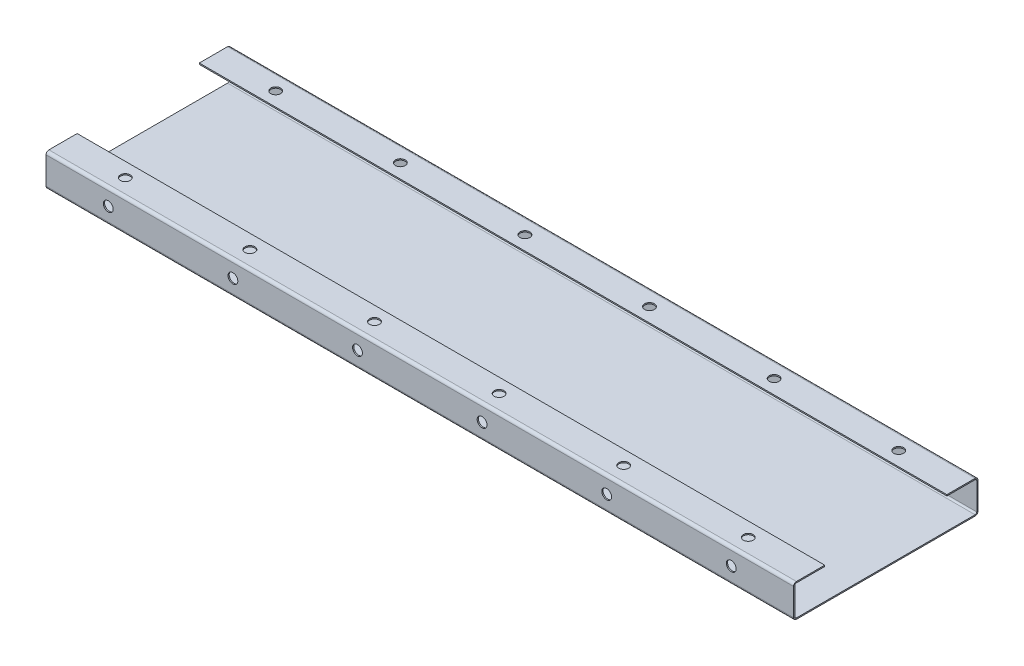
SolidWorks part; units mm, degrees
note: The reader was unsure of these and kept them because the rebuilt part matched: flange length of "Edge-Flange1", "Edge-Flange2".
material "Galvanized Steel"
ref_plane "Front Plane" through (0, 0, 0) normal (0, 0, 1) x (1, 0, 0)
ref_plane "Top Plane" through (0, 0, 0) normal (0, 1, 0) x (1, 0, 0)
ref_plane "Right Plane" through (0, 0, 0) normal (1, 0, 0) x (0, 0, -1)
sketch "Sketch1" plane through (0, 0, 0) normal (0, 1, 0) x (1, 0, 0)
  line L1 (-456, -112.5) -> (456, -112.5)
  line L2 (-456, -112.5) -> (-456, 112.5)
  line L3 (-456, 112.5) -> (456, 112.5)
  line L4 (456, -112.5) -> (456, 112.5)
  line L5 (-456, -112.5) -> (456, 112.5) construction
  line L6 (-456, 112.5) -> (456, -112.5) construction
  point P0 (0, 0)
base flange "Base-Flange1" sketch "Sketch1" thickness 1.5 reverse thickness direction no parameters "D1"=2
edge flange "Edge-Flange1" sketch "Sketch10" flange profiles "Sketch10", "Sketch11" flange angle 90 flange length 40 flange position material inside bend radius 2 thickness 1.5 relief rectangular parameters "D6"=10, "D8"=1
sketch "Sketch10" plane through (0, 0, 112.5) normal (0, 0, 1) x (1, 0, 0)
  line L0 (-456, 0) -> (456, 0) construction
  line L1 (-456, 0) -> (456, 0)
  line L2 (-456, 0) -> (-456, 38.5)
  line L3 (-456, 38.5) -> (456, 38.5)
  line L4 (456, 38.5) -> (456, 0)
sketch "Sketch11" plane through (0, 0, -112.5) normal (0, 0, -1) x (-1, 0, 0)
  line L0 (-456, 0) -> (456, 0) construction
  line L1 (-456, 0) -> (456, 0)
  line L2 (-456, 0) -> (-456, 38.5)
  line L3 (-456, 38.5) -> (456, 38.5)
  line L4 (456, 38.5) -> (456, 0)
bend "EdgeBend1" bend radius 2 bend angle 90 parameters "D5"=1
bend "EdgeBend2" bend radius 2 bend angle 90 parameters "D5"=2
edge flange "Edge-Flange2" sketch "Sketch16" flange profiles "Sketch16", "Sketch17" flange angle 90 flange length 38 flange position material inside bend radius 2 thickness 1.5 relief rectangular parameters "D6"=10, "D8"=1
sketch "Sketch16" plane through (0, 38.5, 111) normal (0, 1, 0) x (1, 0, 0)
  line L2 (-456, 0) -> (-456, 36.5)
  line L3 (-456, 36.5) -> (456, 36.5)
  line L4 (456, 36.5) -> (456, 0)
  line L7 (456, 0) -> (-456, 0) construction
  line L8 (456, 0) -> (-456, 0)
sketch "Sketch17" plane through (0, 38.5, -111) normal (0, 1, 0) x (-1, 0, 0)
  line L0 (456, 0) -> (-456, 0) construction
  line L1 (456, 0) -> (-456, 0)
  line L2 (-456, 0) -> (-456, 36.5)
  line L3 (-456, 36.5) -> (456, 36.5)
  line L4 (456, 36.5) -> (456, 0)
bend "EdgeBend3" bend radius 2 bend angle 90 parameters "D5"=3
bend "EdgeBend4" bend radius 2 bend angle 90 parameters "D5"=4
sketch "Sketch18" plane through (0, 0, 112.5) normal (0, 0, 1) x (1, 0, 0)
  circle A0 centre (380, 18.5) radius 6
  circle A1 centre (228, 18.5) radius 6
  circle A2 centre (76, 18.5) radius 6
  circle A3 centre (-76, 18.5) radius 6
  circle A4 centre (-228, 18.5) radius 6
  circle A5 centre (-380, 18.5) radius 6
  dimension "D1" = 6
extrude "Cut-Extrude1" cut sketch "Sketch18" against normal blind 280
sketch "Sketch19" plane through (0, 38.5, 0) normal (0, 1, 0) x (1, 0, 0)
  circle A0 centre (-380, -91.75) radius 6
  circle A1 centre (-228, -91.75) radius 6
  circle A2 centre (-76, -91.75) radius 6
  circle A3 centre (76, -91.75) radius 6
  circle A4 centre (228, -91.75) radius 6
  circle A5 centre (380, -91.75) radius 6
  circle A6 centre (380, 91.75) radius 6
  circle A7 centre (228, 91.75) radius 6
  circle A8 centre (76, 91.75) radius 6
  circle A9 centre (-76, 91.75) radius 6
  circle A10 centre (-228, 91.75) radius 6
  circle A11 centre (-380, 91.75) radius 6
  dimension "D1" = 6
extrude "Cut-Extrude2" cut sketch "Sketch19" against normal blind 5
sketch "Bend-Lines1" [suppressed] plane through (0, 0, 0) normal (0, 1, 0) x (1, 0, 0)
sketch "Bounding-Box1" [suppressed] plane through (0, 0, 0) normal (0, 1, 0) x (1, 0, 0)
sheet metal parameters "Sheet-Metal1" thickness 1.5 parameters "D1"=2
flat pattern "Flat-Pattern1" [suppressed]
sketch "Bend-Lines2" plane through (0, 0, 0) normal (0, 1, 0) x (1, 0, 0)
sketch3d "Bounding-Box2" [suppressed]
  line L0 (-456, 112.5, 0) -> (456, 112.5, 0) construction
  line L1 (-456, -112.5, 0) -> (456, -112.5, 0) construction
  line L2 (-456, 112.5, 0) -> (-456, -112.5, 0) construction
  line L3 (456, 112.5, 0) -> (456, -112.5, 0) construction
sheet metal parameters "Sheet-Metal2" thickness 1.5 parameters "D1"=2
flat pattern "Flat-Pattern1"
sketch "Bend-Lines2" plane through (0, 0, 0) normal (0, 1, 0) x (1, 0, 0)
  line L0 (456, 111.1598) -> (-456, 111.1598) construction
  line L1 (-456, -111.1598) -> (456, -111.1598) construction
  line L2 (456, 111.1598) -> (-456, 111.1598) construction
  line L3 (-456, -111.1598) -> (456, -111.1598) construction
sketch3d "Bounding-Box2" [suppressed]
  line L0 (456, 149.8197, 0) -> (-456, 149.8197, 0) construction
  line L1 (456, -149.8197, 0) -> (-456, -149.8197, 0) construction
  line L2 (456, 149.8197, 0) -> (456, -149.8197, 0) construction
  line L3 (-456, 149.8197, 0) -> (-456, -149.8197, 0) construction
bend of the flat pattern "Flatten-<EdgeBend1>1"
bend of the flat pattern "Flatten-<EdgeBend2>1"
sheet metal parameters "Sheet-Metal3" thickness 1.5 parameters "D1"=2
flat pattern "Flat-Pattern1"
sketch "Bend-Lines2" plane through (0, 0, 0) normal (0, 1, 0) x (1, 0, 0)
  line L0 (456, 111.1598) -> (-456, 111.1598) construction
  line L1 (-456, -111.1598) -> (456, -111.1598) construction
  line L2 (456, 111.1598) -> (-456, 111.1598) construction
  line L3 (-456, -111.1598) -> (456, -111.1598) construction
  line L4 (456, 148.4795) -> (-456, 148.4795) construction
  line L5 (-456, -148.4795) -> (456, -148.4795) construction
  line L6 (456, 148.4795) -> (-456, 148.4795) construction
  line L7 (-456, -148.4795) -> (456, -148.4795) construction
sketch3d "Bounding-Box2" [suppressed]
  line L0 (456, 185.1394, 0) -> (-456, 185.1394, 0) construction
  line L1 (456, -185.1394, 0) -> (-456, -185.1394, 0) construction
  line L2 (456, 185.1394, 0) -> (456, -185.1394, 0) construction
  line L3 (-456, 185.1394, 0) -> (-456, -185.1394, 0) construction
bend of the flat pattern "Flatten-<EdgeBend1>1"
bend of the flat pattern "Flatten-<EdgeBend2>1"
bend of the flat pattern "Flatten-<EdgeBend3>1"
bend of the flat pattern "Flatten-<EdgeBend4>1"
sheet metal parameters "Sheet-Metal4" thickness 1.5 parameters "D1"=2
flat pattern "Flat-Pattern1"
sketch "Bend-Lines2" plane through (0, 0, 0) normal (0, 1, 0) x (1, 0, 0)
  line L0 (456, 111.1598) -> (-456, 111.1598) construction
  line L1 (-456, -111.1598) -> (456, -111.1598) construction
  line L2 (456, 111.1598) -> (-456, 111.1598) construction
  line L3 (-456, -111.1598) -> (456, -111.1598) construction
  line L4 (456, 148.4795) -> (-456, 148.4795) construction
  line L5 (-456, -148.4795) -> (456, -148.4795) construction
  line L6 (456, 148.4795) -> (-456, 148.4795) construction
  line L7 (-456, -148.4795) -> (456, -148.4795) construction
sketch3d "Bounding-Box2" [suppressed]
  line L0 (456, 185.1394, 0) -> (-456, 185.1394, 0) construction
  line L1 (456, -185.1394, 0) -> (-456, -185.1394, 0) construction
  line L2 (456, 185.1394, 0) -> (456, -185.1394, 0) construction
  line L3 (-456, 185.1394, 0) -> (-456, -185.1394, 0) construction
bend of the flat pattern "Flatten-<EdgeBend1>1"
bend of the flat pattern "Flatten-<EdgeBend2>1"
bend of the flat pattern "Flatten-<EdgeBend3>1"
bend of the flat pattern "Flatten-<EdgeBend4>1"
sheet metal parameters "Sheet-Metal5" thickness 1.5 parameters "D1"=2
flat pattern "Flat-Pattern1"
sketch "Bend-Lines2" plane through (0, 0, 0) normal (0, 1, 0) x (1, 0, 0)
  line L0 (456, 111.1598) -> (-456, 111.1598) construction
  line L1 (-456, -111.1598) -> (456, -111.1598) construction
  line L2 (456, 111.1598) -> (-456, 111.1598) construction
  line L3 (-456, -111.1598) -> (456, -111.1598) construction
  line L4 (456, 148.4795) -> (-456, 148.4795) construction
  line L5 (-456, -148.4795) -> (456, -148.4795) construction
  line L6 (456, 148.4795) -> (-456, 148.4795) construction
  line L7 (-456, -148.4795) -> (456, -148.4795) construction
sketch3d "Bounding-Box2" [suppressed]
  line L0 (456, 185.1394, 0) -> (-456, 185.1394, 0) construction
  line L1 (456, -185.1394, 0) -> (-456, -185.1394, 0) construction
  line L2 (456, 185.1394, 0) -> (456, -185.1394, 0) construction
  line L3 (-456, 185.1394, 0) -> (-456, -185.1394, 0) construction
bend of the flat pattern "Flatten-<EdgeBend1>1"
bend of the flat pattern "Flatten-<EdgeBend2>1"
bend of the flat pattern "Flatten-<EdgeBend3>1"
bend of the flat pattern "Flatten-<EdgeBend4>1"
